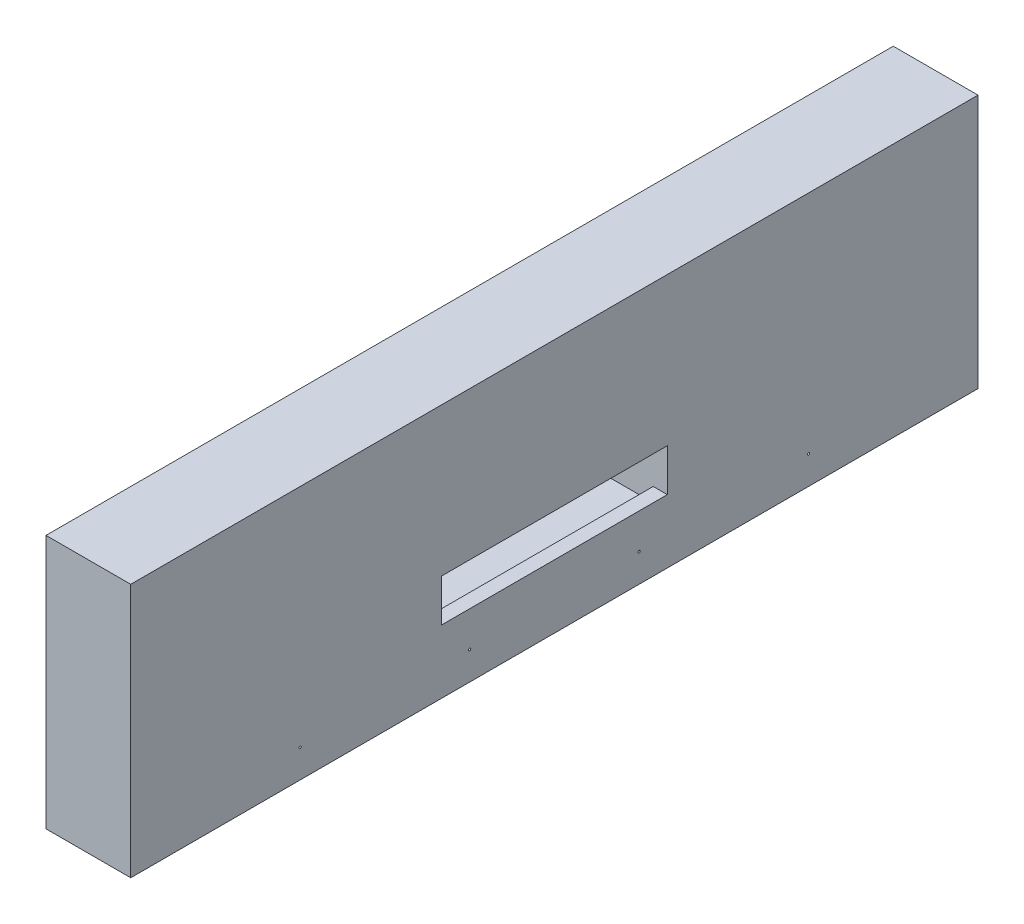
SolidWorks part; units mm, degrees
ref_plane "Front Plane" through (0, 0, 0) normal (0, 0, 1) x (1, 0, 0)
ref_plane "Top Plane" through (0, 0, 0) normal (0, 1, 0) x (1, 0, 0)
ref_plane "Right Plane" through (0, 0, 0) normal (1, 0, 0) x (0, 0, -1)
sketch "Sketch1" plane through (0, 0, 0) normal (1, 0, 0) x (0, 0, -1)
  line L1 (0, 0) -> (762, 0)
  line L2 (0, 0) -> (0, 228.6)
  line L3 (0, 228.6) -> (762, 228.6)
  line L4 (762, 0) -> (762, 228.6)
  dimension "D1" = 762
  dimension "D2" = 228.6
extrude "Boss-Extrude1" add sketch "Sketch1" along normal blind 76.2
sketch "Sketch2" plane through (0, 0, 0) normal (-1, 0, 0) x (0, 0, 1)
  line L1 (-482.6, 44.45) -> (-279.4, 44.45)
  line L2 (-482.6, 44.45) -> (-482.6, 139.7)
  line L3 (-482.6, 139.7) -> (-279.4, 139.7)
  line L4 (-279.4, 44.45) -> (-279.4, 139.7)
  line L6 (0, 0) -> (-762, 0) construction
  line L7 (-762, 0) -> (-762, 228.6) construction
  point P6 (-381, 139.7)
  dimension "D1" = 44.45
  dimension "D2" = 381
  dimension "D3" = 95.25
  dimension "D4" = 203.2
extrude "Cut-Extrude1" cut sketch "Sketch2" against normal blind 63.5
sketch "Sketch3" plane through (63.5, 0, 0) normal (-1, 0, 0) x (0, 0, 1)
  line L0 (-279.4, 44.45) -> (-279.4, 139.7) construction
  line L1 (-482.6, 95.25) -> (-279.4, 95.25)
  line L2 (-482.6, 95.25) -> (-482.6, 57.15)
  line L3 (-482.6, 57.15) -> (-279.4, 57.15)
  line L4 (-279.4, 95.25) -> (-279.4, 57.15)
  line L5 (-482.6, 44.45) -> (-279.4, 44.45) construction
  line L6 (-482.6, 139.7) -> (-482.6, 44.45) construction
  dimension "D1" = 12.7
  dimension "D2" = 38.1
extrude "Cut-Extrude2" cut sketch "Sketch3" against normal through all
fillet "Fillet1" radius 25.4 2 edges at (31.75, 139.7, -279.4) (31.75, 139.7, -482.6)
sketch "Sketch4" plane through (0, 0, 0) normal (-1, 0, 0) x (0, 0, 1)
  line L1 (-762, 0) -> (-762, 228.6) construction
  line L2 (0, 0) -> (-762, 0) construction
  circle A0 centre (-609.6, 25.4) radius 1.016
  dimension "D3" = 2.032
  dimension "D1" = 152.4
  dimension "D2" = 25.4
extrude "Cut-Extrude3" cut sketch "Sketch4" against normal through all
pattern_linear "LPattern1" count 4 spacing 152.4 along (0, 0, 1) of "Cut-Extrude3"
